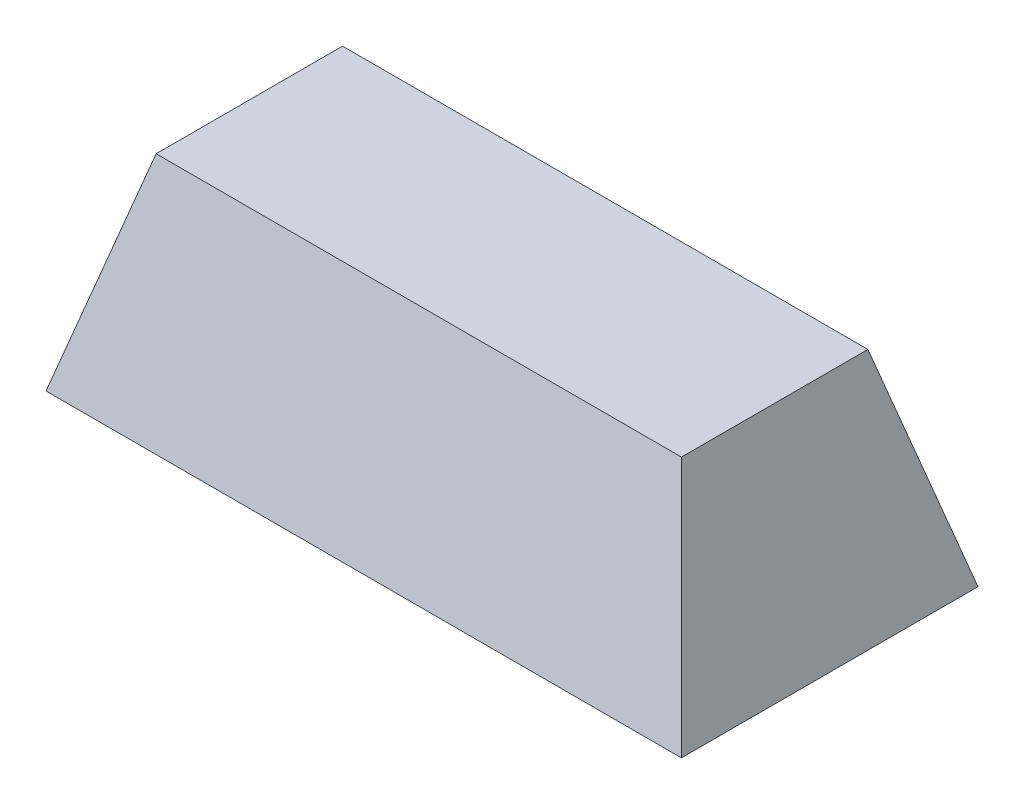
SolidWorks part; units mm, degrees
ref_plane "Face" through (0, 0, 0) normal (0, 0, 1) x (1, 0, 0)
ref_plane "Dessus" through (0, 0, 0) normal (0, 1, 0) x (1, 0, 0)
ref_plane "Droite" through (0, 0, 0) normal (1, 0, 0) x (0, 0, -1)
sketch "Esquisse2" plane through (0, 0, 0) normal (0, 1, 0) x (1, 0, 0)
  line L1 (0, 0) -> (150, 0)
  line L2 (0, 0) -> (0, 70)
  line L3 (0, 70) -> (150, 70)
  line L4 (150, 0) -> (150, 70)
  dimension "D1" = 70
  dimension "D2" = 150
extrude "Extrusion1" add sketch "Esquisse2" along normal blind 48.5
sketch "Esquisse3" plane through (0, 0, 0) normal (0, 0, 1) x (1, 0, 0)
  line L0 (0, 0) -> (0, 48.5)
  line L1 (0, 48.5) -> (12.9955, 48.5)
  line L2 (0, 48.5) -> (150, 48.5) construction
  line L3 (12.9955, 48.5) -> (0, 0)
  line L4 (75, 48.5) -> (75, 0) construction
  line L5 (0, 0) -> (150, 0) construction
  line L6 (137.0045, 48.5) -> (150, 0)
  line L7 (150, 48.5) -> (137.0045, 48.5)
  line L8 (150, 0) -> (150, 48.5)
  dimension "D1" = 75
extrude "Extrusion2" cut sketch "Esquisse3" against normal up to next
chamfer "Chanfrein1" distance 48.5 angle 15 1 edges at (75, 48.5, -70) first distance on face at (75, 24.25, -70)
chamfer "Chanfrein2" distance 48.5 angle 15 1 edges at (75, 48.5, 0) first distance on face at (75, 24.25, 0)
